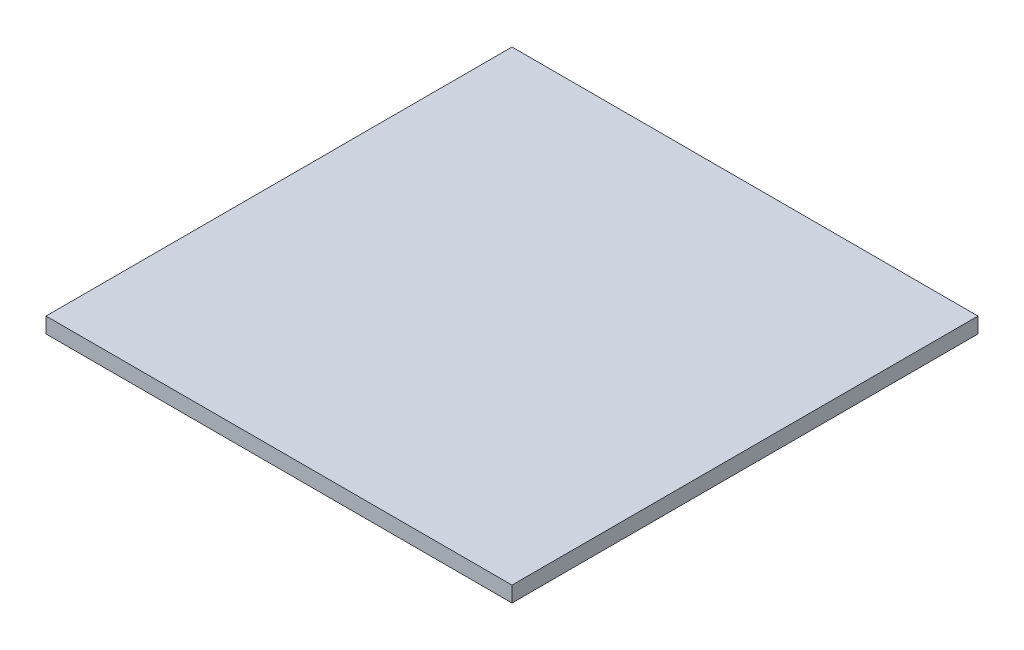
SolidWorks part; units mm, degrees
ref_plane "Front Plane" through (0, 0, 0) normal (0, 0, 1) x (1, 0, 0)
ref_plane "Top Plane" through (0, 0, 0) normal (0, 1, 0) x (1, 0, 0)
ref_plane "Right Plane" through (0, 0, 0) normal (1, 0, 0) x (0, 0, -1)
sketch "Sketch1" plane through (0, 0, 0) normal (0, 1, 0) x (1, 0, 0)
  line L0 (-150, 150) -> (150, -150) construction
  line L1 (-150, 150) -> (150, 150)
  line L2 (-150, 150) -> (-150, -150)
  line L3 (-150, -150) -> (150, -150)
  line L4 (150, 150) -> (150, -150)
  dimension "D1" = 300
  dimension "D2" = 300
extrude "Boss-Extrude1" add sketch "Sketch1" along normal blind 10
sketch "Sketch2" plane through (0, 10, 0) normal (0, 1, 0) x (1, 0, 0)
  line L0 (-150, 150) -> (-150, -150) construction
  line L1 (150, 150) -> (-150, 150) construction
  point P0 (0, 0)
  point P1 (0, 0)
  point P4 (-150, 0)
  point P7 (0, 0)
  point P8 (0, 150)
ref_axis "Axis1" through (0, 10, 0) along (0, 1, 0)
